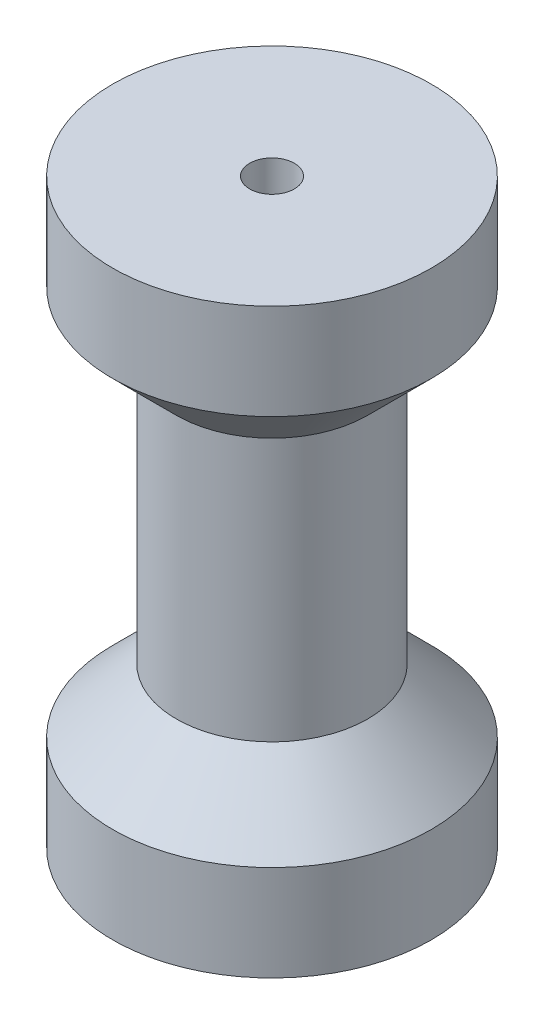
SolidWorks part; units mm, degrees
material "PA Type 6"
ref_plane "Front Plane" through (0, 0, 0) normal (0, 0, 1) x (1, 0, 0)
ref_plane "Top Plane" through (0, 0, 0) normal (0, 1, 0) x (1, 0, 0)
ref_plane "Right Plane" through (0, 0, 0) normal (1, 0, 0) x (0, 0, -1)
sketch "Sketch1" plane through (0, 0, 0) normal (0, 0, 1) x (1, 0, 0)
  line L0 (1.4, 0) -> (1.4, 36.5)
  line L1 (1.4, 36.5) -> (10, 36.5)
  line L2 (6, 30.5) -> (6, 6)
  line L3 (10, 0) -> (1.4, 0)
  line L4 (0, -42.8219) -> (0, 42.8219) construction
  line L5 (10, 36.5) -> (10, 30.5)
  line L6 (10, 30.5) -> (6, 30.5)
  line L7 (10, 0) -> (10, 6)
  line L8 (10, 6) -> (6, 6)
  point P8 (0, 0)
  dimension "D1" = 36.5
  dimension "D2" = 6
  dimension "D3" = 1.4
  dimension "D4" = 6
  dimension "D5" = 10
revolve "Revolve1" add sketch "Sketch1" angle 360 about L4
chamfer "Chamfer1" distance 4 angle 45 2 edges at (6, 6, 0) (6, 30.5, 0)
